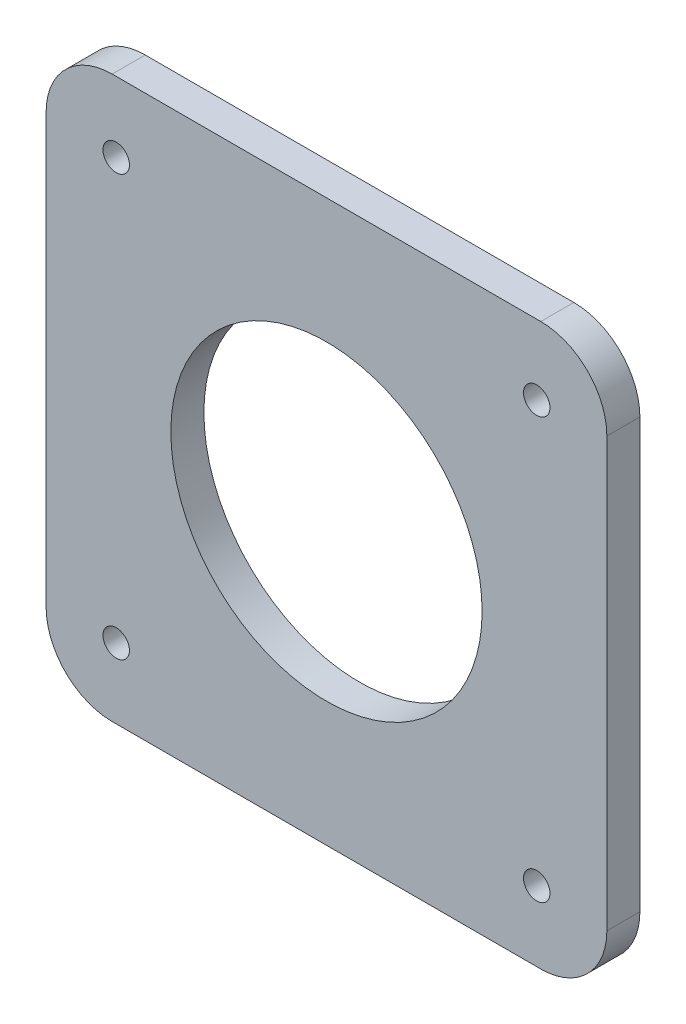
SolidWorks part; units mm, degrees
ref_plane "Front Plane" through (0, 0, 0) normal (0, 0, 1) x (1, 0, 0)
ref_plane "Top Plane" through (0, 0, 0) normal (0, 1, 0) x (1, 0, 0)
ref_plane "Right Plane" through (0, 0, 0) normal (1, 0, 0) x (0, 0, -1)
sketch "Sketch1" plane through (0, 0, 0) normal (0, 0, 1) x (1, 0, 0)
  line L1 (-5.5355, 65.4307) -> (59.3145, 65.4307)
  line L2 (-15.5355, 55.4307) -> (-15.5355, -9.4193)
  line L3 (-5.5355, -19.4193) -> (59.3145, -19.4193)
  line L4 (69.3145, 55.4307) -> (69.3145, -9.4193)
  circle A0 centre (26.8895, 23.0057) radius 23.55
  arc A1 (59.3145, 65.4307) -> (69.3145, 55.4307) centre (59.3145, 55.4307) cw
  arc A2 (59.3145, -19.4193) -> (69.3145, -9.4193) centre (59.3145, -9.4193) ccw
  arc A3 (-15.5355, -9.4193) -> (-5.5355, -19.4193) centre (-5.5355, -9.4193) ccw
  arc A4 (-5.5355, 65.4307) -> (-15.5355, 55.4307) centre (-5.5355, 55.4307) ccw
  circle A5 centre (-4.9255, 54.8207) radius 2
  circle A6 centre (-4.9255, -8.8093) radius 2
  circle A7 centre (58.7045, 54.8207) radius 2
  circle A8 centre (58.7045, -8.8093) radius 2
  dimension "D1" = 10
  dimension "D2" = 10
  dimension "D3" = 10
  dimension "D4" = 10
  dimension "D5" = 47.1
extrude "Boss-Extrude1" add sketch "Sketch1" along normal blind 5
